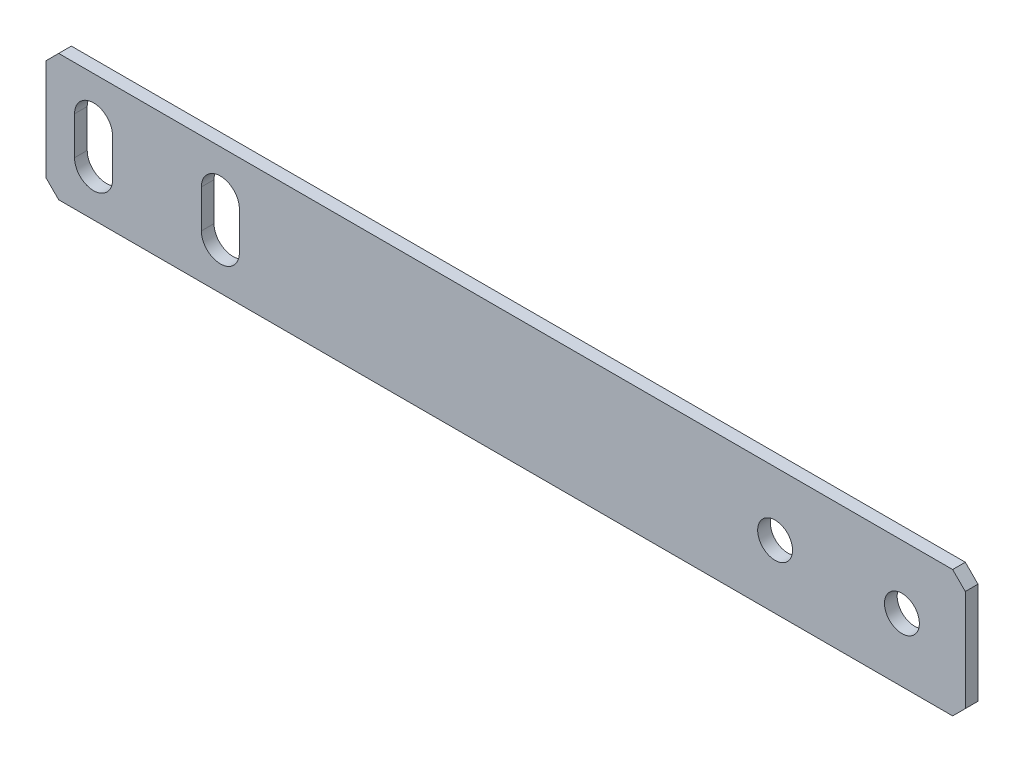
SolidWorks part; units mm, degrees
ref_plane "Front Plane" through (0, 0, 0) normal (0, 0, 1) x (1, 0, 0)
ref_plane "Top Plane" through (0, 0, 0) normal (0, 1, 0) x (1, 0, 0)
ref_plane "Right Plane" through (0, 0, 0) normal (1, 0, 0) x (0, 0, -1)
sketch "Sketch1" plane through (0, 0, 0) normal (0, 0, 1) x (1, 0, 0)
  line L0 (-65, -3) -> (-65, 3) construction
  line L1 (72.5, 10) -> (-72.5, 10)
  line L2 (72.5, 10) -> (72.5, -10)
  line L3 (72.5, -10) -> (-72.5, -10)
  line L4 (-72.5, 10) -> (-72.5, -10)
  line L5 (72.5, 10) -> (-72.5, -10) construction
  line L6 (72.5, -10) -> (-72.5, 10) construction
  line L7 (-68, -3) -> (-68, 3)
  line L8 (-62, -3) -> (-62, 3)
  line L9 (-45, -3) -> (-45, 3) construction
  line L10 (-48, -3) -> (-48, 3)
  line L11 (-42, -3) -> (-42, 3)
  circle A0 centre (62.5, 0) radius 2.75
  circle A1 centre (42.5, 0) radius 2.75
  arc A4 (-68, -3) -> (-62, -3) centre (-65, -3) ccw
  arc A5 (-62, 3) -> (-68, 3) centre (-65, 3) ccw
  arc A6 (-48, -3) -> (-42, -3) centre (-45, -3) ccw
  arc A7 (-42, 3) -> (-48, 3) centre (-45, 3) ccw
  point P0 (0, 0)
  point P12 (-65, 0)
  point P18 (-45, 0)
  dimension "D1" = 5.5
  dimension "D2" = 20
  dimension "D9" = 3
  dimension "D3" = 145
  dimension "D4" = 20
  dimension "D5" = 10
  dimension "D6" = 7.5
  dimension "D7" = 20
  dimension "D8" = 6
extrude "Boss-Extrude1" add sketch "Sketch1" along normal blind 2
chamfer "Chamfer1" distance 2 angle 45 4 edges at (-72.5, -10, 1) (72.5, -10, 1) (72.5, 10, 1) (-72.5, 10, 1)
